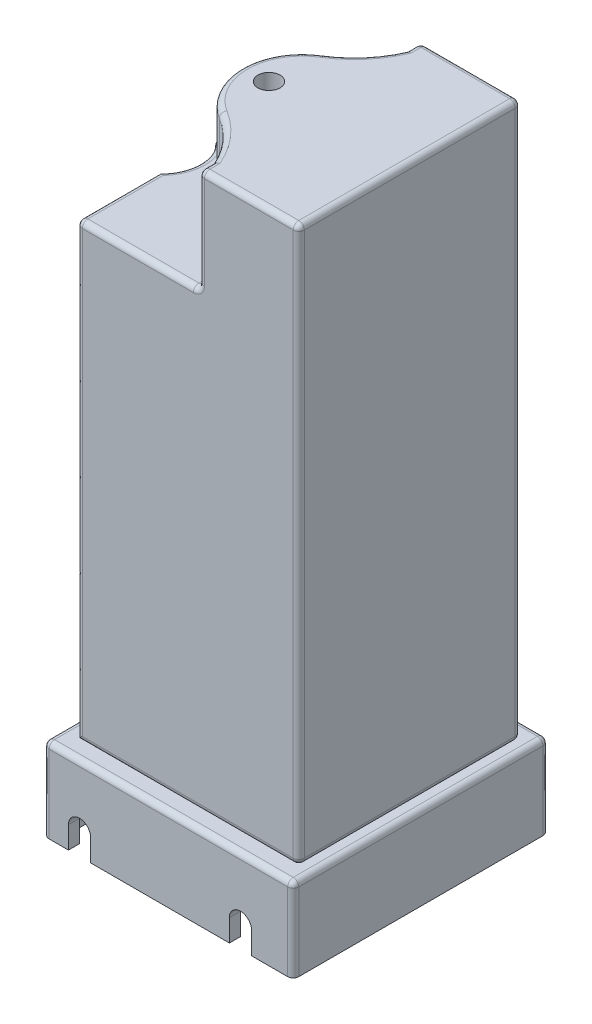
SolidWorks part; units mm, degrees
ref_plane "Front Plane" through (0, 0, 0) normal (0, 0, 1) x (1, 0, 0)
ref_plane "Top Plane" through (0, 0, 0) normal (0, 1, 0) x (1, 0, 0)
ref_plane "Right Plane" through (0, 0, 0) normal (1, 0, 0) x (0, 0, -1)
sketch "Sketch1" plane through (0, 0, 0) normal (0, 1, 0) x (1, 0, 0)
  line L1 (-200, -200) -> (200, -200)
  line L2 (-200, -200) -> (-200, 200)
  line L3 (-200, 200) -> (200, 200)
  line L4 (200, -200) -> (200, 200)
  line L5 (-200, -200) -> (200, 200) construction
  line L6 (-200, 200) -> (200, -200) construction
  point P0 (0, 0)
  dimension "D1" = 400
  dimension "D2" = 400
extrude "Boss-Extrude1" add sketch "Sketch1" along normal blind 1000
sketch "Sketch2" plane through (0, 0, 200) normal (0, 0, 1) x (1, 0, 0)
  line L0 (-200, 900) -> (20, 900)
  line L1 (-200, 1000) -> (-200, 0) construction
  line L2 (20, 900) -> (20, 812.4135)
  line L3 (20, 812.4135) -> (-200, 812.4135)
  line L4 (-200, 900) -> (-200, 812.4135)
  line L5 (-200, 1000) -> (200, 1000) construction
  line L6 (200, 1000) -> (200, 0) construction
  point P5 (-200, 799.9131)
  dimension "D1" = 100
  dimension "D2" = 180
extrude "Cut-Extrude1" cut sketch "Sketch2" against normal blind 1000
sketch "Sketch3" plane through (0, 1000, 0) normal (0, 1, 0) x (1, 0, 0)
  line L0 (20, 200) -> (20, -200) construction
  line L5 (-220, 0) -> (220, 0) construction
  line L7 (20, 200) -> (-200, 200)
  line L8 (-200, 200) -> (-200, -200)
  line L9 (-200, -200) -> (20, -200)
  line L11 (20, 174.0779) -> (20, 200)
  line L12 (20, -174.0779) -> (20, -200)
  arc A2 (-51.1058, 92.0718) -> (-51.1058, -92.0718) centre (5.9968, 0) ccw
  arc A4 (20, 174.0779) -> (-51.1058, 92.0718) centre (-147.4819, 247.4676) cw
  arc A5 (20, -174.0779) -> (-51.1058, -92.0718) centre (-147.4819, -247.4676) ccw
extrude "Cut-Extrude2" cut sketch "Sketch3" against normal up to next
fillet "Fillet7" radius 10 3 edges at (-9.3279, 900, 127.6773) (-9.3279, 900, -127.6773) (-102.3448, 900, 0)
sketch "Sketch6" plane through (0, 812.4135, 0) normal (0, 1, 0) x (1, 0, 0)
  line L0 (-200, 200) -> (-200, -200)
  line L1 (-200, 50.4336) -> (-200, -50.4336)
  arc A0 (-200, 50.4336) -> (-200, -50.4336) centre (-248.9525, 0) cw
  point P8 (-200, 0)
extrude "Cut-Extrude3" cut sketch "Sketch6" against normal blind 1119 contours A0 L0
sketch "Sketch7" plane through (-200, 0, 0) normal (-1, 0, 0) x (0, 0, 1)
  line L10 (199.0843, 709.2094) -> (-198.3802, 709.2094)
  line L11 (199.0843, 709.2094) -> (199.0843, 712.8999)
  line L12 (199.0843, 712.8999) -> (-198.3802, 712.8999)
  line L13 (-198.3802, 709.2094) -> (-198.3802, 712.8999)
extrude "Cut-Extrude4" cut sketch "Sketch7" against normal blind 51
pattern_linear "LPattern1" count 5 spacing 150 along (0, -1, 0) of "Cut-Extrude4"
sketch "Sketch8" plane through (0, 1000, 0) normal (0, 1, 0) x (1, 0, 0)
  circle A0 centre (-53.7308, 0) radius 20
  dimension "D1" = 40
extrude "Cut-Extrude5" cut sketch "Sketch8" against normal up to surface (100 mm away) up to face at (-22.4137, 900, 0)
fillet "Fillet8" radius 10 16 edges at (20, 906.2068, -200) (-90, 812.4135, 200) (-9.3279, 1000, -127.6773) (-9.3279, 1000, 127.6773) (20, 1000, -187.039) (20, 1000, 187.039) (110, 1000, -200) (200, 1000, 0) (110, 1000, 200) (-102.3448, 1000, 0) (-90, 812.4135, -200) (-178.6681, 812.4135, 0) (-200, 812.4135, 125.2168) (-200, 812.4135, -125.2168) (20, 812.4135, 0) (20, 906.2068, 200)
ref_plane "Plane1" through (0, 759.2094, 0) normal (0, 1, 0) x (1, 0, 0)
sketch "Sketch9" plane through (0, 759.2094, 0) normal (0, 1, 0) x (1, 0, 0)
  arc A2 (-192.8752, -42.3703) -> (-191.9733, 41.1493) centre (-161.5745, -0.9436) cw
ref_plane "Plane2" through (-192.8752, 759.2094, 42.3703) normal (-0.7979, 0, -0.6028) x (-0.6028, 0, 0.7979)
sketch "Sketch10" plane through (-192.8752, 759.2094, 42.3703) normal (-0.7979, 0, -0.6028) x (-0.6028, 0, 0.7979)
  circle A0 centre (0, 0) radius 7.5
  dimension "D1" = 15
sweep "Sweep1" add profiles "Sketch10" path "Sketch9"
pattern_linear "LPattern2" count 6 spacing 140 along (0, -1, 0) of "Sweep1"
fillet "Fillet9" radius 2 2 edges at (-189.1315, 764.698, -36.8964) (-196.7751, 763.5492, 47.0894)
fillet "Fillet10" radius 2 10 edges at (-189.1315, 64.698, -36.8964) (-196.7751, 63.5492, 47.0894) (-189.7501, 205.5842, -37.881) (-196.2673, 204.4587, 46.5207) (-189.7501, 345.5842, -37.881) (-196.2673, 344.4587, 46.5207) (-189.7501, 485.5842, -37.881) (-196.2673, 484.4587, 46.5207) (-189.1315, 624.698, -36.8964) (-196.7751, 623.5492, 47.0894)
fillet "Fillet11" radius 10 10 edges at (197.0711, 997.0711, 197.0711) (-197.0711, 809.4846, 197.0711) (-197.0711, 809.4846, -197.0711) (197.0711, 997.0711, -197.0711) (200, 495, 200) (0, 0, 200) (-200, 401.2068, 200) (-200, 401.2068, -200) (0, 0, -200) (200, 495, -200)
fillet "Fillet12" radius 10 3 edges at (197.0711, 2.9289, 197.0711) (197.0711, 2.9289, -197.0711) (200, 0, 0)
sketch "Sketch11" plane through (0, 0, 0) normal (0, -1, 0) x (-1, 0, 0)
  line L0 (200, -50.4336) -> (200, -190) construction
  line L1 (230, -230) -> (-220, -230)
  line L2 (230, -230) -> (230, 230)
  line L3 (230, 230) -> (-220, 230)
  line L4 (-220, -230) -> (-220, 230)
  line L5 (190, -200) -> (-190, -200) construction
  line L6 (-190, 190) -> (-190, -190) construction
  line L7 (-190, 200) -> (190, 200) construction
  dimension "D1" = 30
  dimension "D2" = 30
  dimension "D3" = 30
  dimension "D4" = 30
extrude "Boss-Extrude2" add sketch "Sketch11" along normal blind 150
sketch "Sketch12" plane through (0, -150, 0) normal (0, -1, 0) x (-1, 0, 0)
  line L0 (230, -230) -> (230, 230) construction
  line L1 (210, 210) -> (-200, 210)
  line L2 (210, 210) -> (210, -210)
  line L3 (210, -210) -> (-200, -210)
  line L4 (-200, 210) -> (-200, -210)
  line L5 (210, 210) -> (-200, -210) construction
  line L6 (210, -210) -> (-200, 210) construction
  line L7 (230, 230) -> (-220, 230) construction
  line L10 (-220, 230) -> (-220, -230) construction
  line L11 (-220, -230) -> (230, -230) construction
  point P0 (0, 0)
  point P10 (-16.4301, -15.6477)
  point P11 (0, 0)
  dimension "D1" = 20
  dimension "D2" = 20
  dimension "D3" = 20
  dimension "D4" = 20
extrude "Cut-Extrude6" cut sketch "Sketch12" against normal blind 130
sketch "Sketch13" plane through (0, 0, 230) normal (0, 0, 1) x (1, 0, 0)
  line L0 (-165, -110.3285) -> (-165, -180.3285) construction
  line L1 (-145, -110.3285) -> (-145, -180.3285)
  line L2 (-185, -110.3285) -> (-185, -180.3285)
  line L3 (125, -110.3285) -> (125, -180.3285) construction
  line L4 (145, -110.3285) -> (145, -180.3285)
  line L5 (105, -110.3285) -> (105, -180.3285)
  line L6 (220, -150) -> (220, 0) construction
  arc A0 (-145, -110.3285) -> (-185, -110.3285) centre (-165, -110.3285) ccw
  arc A1 (-185, -180.3285) -> (-145, -180.3285) centre (-165, -180.3285) ccw
  arc A2 (145, -110.3285) -> (105, -110.3285) centre (125, -110.3285) ccw
  arc A3 (105, -180.3285) -> (145, -180.3285) centre (125, -180.3285) ccw
  point P2 (-165, -145.3285)
  point P7 (125, -145.3285)
  point P14 (0, 0)
  dimension "D1" = 20
  dimension "D2" = 20
  dimension "D3" = 70
  dimension "D4" = 70
  dimension "D5" = 250
  dimension "D6" = 75
extrude "Cut-Extrude7" cut sketch "Sketch13" against normal through all
fillet "Fillet13" radius 10 8 edges at (220, -75, 230) (220, 0, 0) (220, -75, -230) (-5, 0, -230) (-230, -75, -230) (-230, -75, 230) (-230, 0, 0) (-5, 0, 230)
